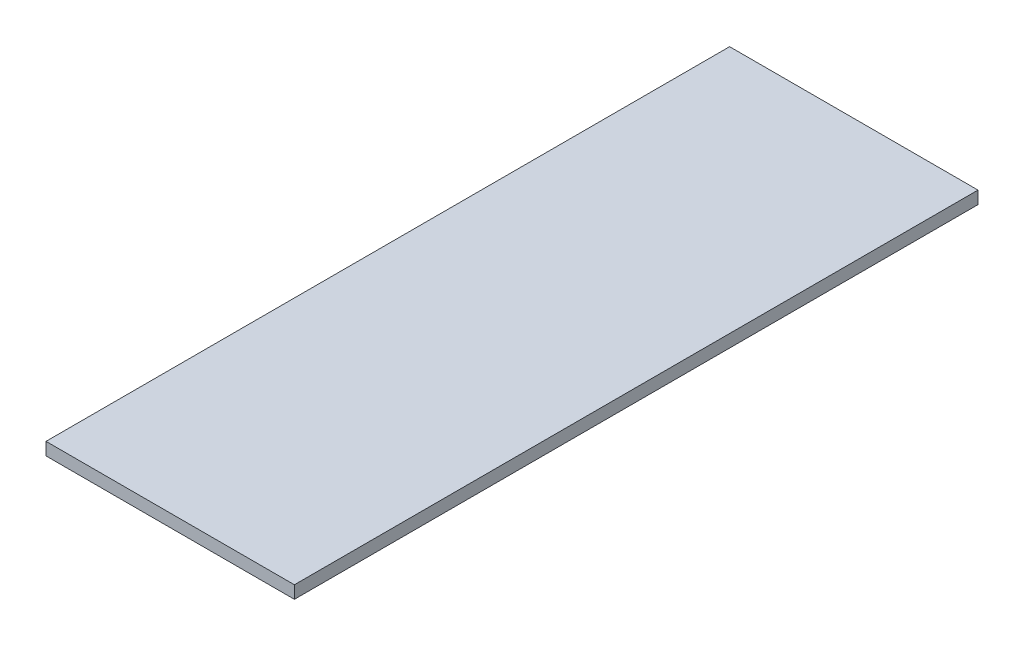
SolidWorks part; units mm, degrees
ref_plane "Front Plane" through (0, 0, 0) normal (0, 0, 1) x (1, 0, 0)
ref_plane "Top Plane" through (0, 0, 0) normal (0, 1, 0) x (1, 0, 0)
ref_plane "Right Plane" through (0, 0, 0) normal (1, 0, 0) x (0, 0, -1)
sketch "Sketch1" plane through (0, 0, 0) normal (0, 1, 0) x (1, 0, 0)
  line L5 (59.944, -164.973) -> (-59.944, -164.973)
  line L6 (59.944, -164.973) -> (59.944, 164.973)
  line L7 (59.944, 164.973) -> (-59.944, 164.973)
  line L9 (59.944, -164.973) -> (-59.944, 164.973) construction
  line L10 (59.944, 164.973) -> (-59.944, -164.973) construction
  line L12 (-59.944, -164.973) -> (-59.944, 164.973)
  point P0 (0, 0)
  dimension "D1" = 329.946
  dimension "D3" = 119.888
extrude "Boss-Extrude1" add sketch "Sketch1" along normal blind 6.096
sketch "Sketch4" plane through (0, 0, 0) normal (0, -1, 0) x (1, 0, 0)
  line L0 (-63.5, 122.5) -> (-63.5, 0) construction
  line L1 (-63.5, 0) -> (0, 0) construction
  line L2 (-63.5, 0) -> (-63.5, -122.5) construction
  line L3 (59.944, 164.973) -> (59.944, -164.973) construction
  circle A2 centre (-63.5, 122.5) radius 12.5
  circle A3 centre (-63.5, -122.5) radius 12.5
  point P11 (59.944, 0)
  dimension "D2" = 25
  dimension "D1" = 122.5
  dimension "D3" = 63.5
  dimension "D4" = 63.5
sketch "Sketch6" plane through (0, 0, 0) normal (0, -1, 0) x (1, 0, 0)
  line L10 (-59.944, 164.973) -> (59.944, 164.973) construction
  line L12 (59.944, -164.973) -> (-16.256, -164.973)
  line L13 (59.944, -164.973) -> (59.944, -114.173)
  line L14 (59.944, -114.173) -> (-16.256, -114.173)
  line L15 (-16.256, -164.973) -> (-16.256, -114.173)
  line L16 (59.944, 164.973) -> (-16.256, 164.973)
  line L17 (59.944, 164.973) -> (59.944, 114.173)
  line L18 (59.944, 114.173) -> (-16.256, 114.173)
  line L19 (-16.256, 164.973) -> (-16.256, 114.173)
  line L20 (59.944, 164.973) -> (59.944, -164.973) construction
  line L21 (59.944, -164.973) -> (-59.944, -164.973) construction
  dimension "D1" = 76.2
  dimension "D2" = 50.8
fillet "Fillet3" radius 38.1 rebuild error yes
fillet "Fillet4" radius 50.8 rebuild error yes
